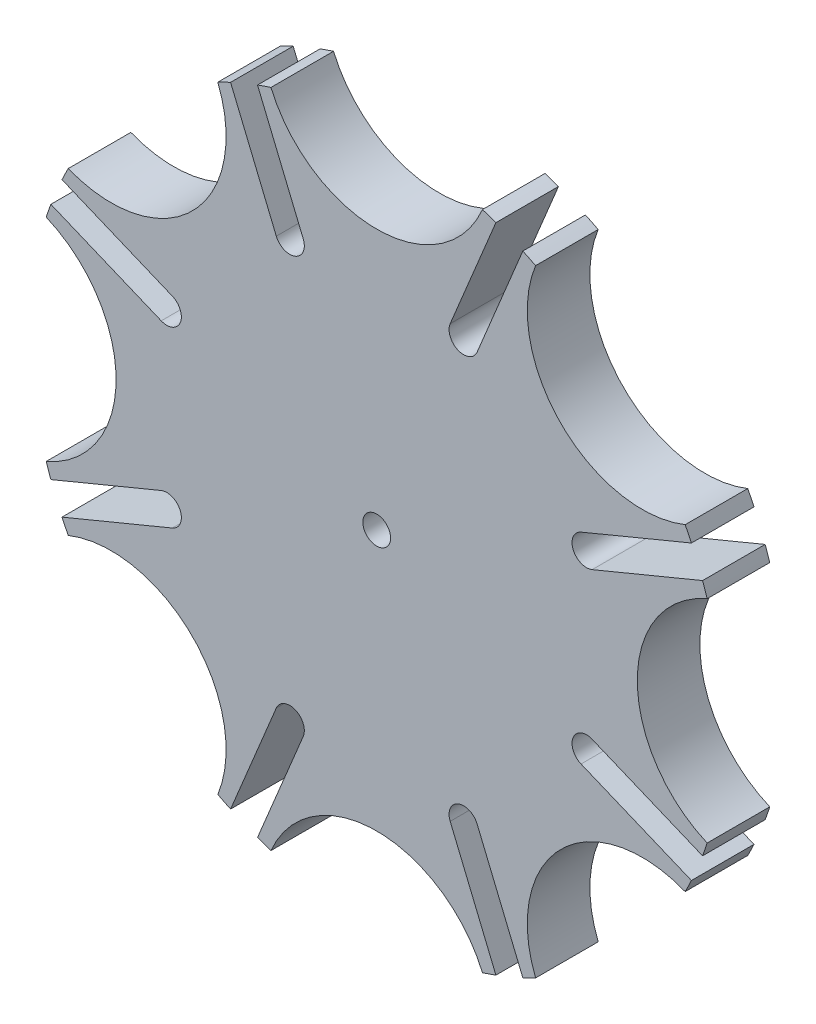
SolidWorks part; units mm, degrees
ref_plane "Front Plane" through (0, 0, 0) normal (0, 0, 1) x (1, 0, 0)
ref_plane "Top Plane" through (0, 0, 0) normal (0, 1, 0) x (1, 0, 0)
ref_plane "Right Plane" through (0, 0, 0) normal (1, 0, 0) x (0, 0, -1)
sketch "Croquis1" plane through (0, 0, 0) normal (0, 0, 1) x (1, 0, 0)
  line L0 (0, 0) -> (-15.1187, 6.2624) construction
  line L1 (0, 0) -> (-18, 0) construction
  line L2 (0, 0) -> (33.8007, 14.0007) construction
  line L3 (0, 0) -> (-10.0606, 4.1672)
  line L4 (-10.0606, 4.1672) -> (-15.364, 6.364) construction
  line L5 (-10.3278, 3.5219) -> (-15.6312, 5.7187)
  line L6 (-9.7933, 4.8125) -> (-15.0967, 7.0092)
  line L7 (-18, 0) -> (-15.364, 6.364) construction
  line L8 (-4.1672, 10.0606) -> (-6.364, 15.364) construction
  line L9 (-4.8125, 9.7933) -> (-7.0092, 15.0967)
  line L10 (-3.5219, 10.3278) -> (-5.7187, 15.6312)
  line L11 (4.1672, 10.0606) -> (6.364, 15.364) construction
  line L12 (3.5219, 10.3278) -> (5.7187, 15.6312)
  line L13 (4.8125, 9.7933) -> (7.0092, 15.0967)
  line L14 (10.0606, 4.1672) -> (15.364, 6.364) construction
  line L45 (-16.2663, 6.7899) -> (-19.2031, 0.5679)
  line L46 (-16.7477, -0.4492) -> (-14.4248, 6.0271)
  line L60 (9.7933, 4.8125) -> (15.0967, 7.0092)
  line L75 (10.3278, 3.5219) -> (15.6312, 5.7187)
  line L82 (10.0606, -4.1672) -> (15.364, -6.364) construction
  line L85 (10.3278, -3.5219) -> (15.6312, -5.7187)
  line L88 (9.7933, -4.8125) -> (15.0967, -7.0092)
  line L91 (4.1672, -10.0606) -> (6.364, -15.364) construction
  line L92 (4.8125, -9.7933) -> (7.0092, -15.0967)
  line L93 (3.5219, -10.3278) -> (5.7187, -15.6312)
  line L94 (-4.1672, -10.0606) -> (-6.364, -15.364) construction
  line L95 (-3.5219, -10.3278) -> (-5.7187, -15.6312)
  line L96 (-4.8125, -9.7933) -> (-7.0092, -15.0967)
  line L97 (-10.0606, -4.1672) -> (-15.364, -6.364) construction
  line L98 (-9.7933, -4.8125) -> (-15.0967, -7.0092)
  line L99 (-10.3278, -3.5219) -> (-15.6312, -5.7187)
  circle A0 centre (0, 0) radius 16.6298
  circle A7 centre (-18, 0) radius 5.5106
  arc A8 (-10.3278, 3.5219) -> (-9.7933, 4.8125) centre (-10.0606, 4.1672) ccw
  arc A9 (-15.0967, 7.0092) -> (-15.6312, 5.7187) centre (-15.364, 6.364) ccw
  circle A10 centre (-12.7279, 12.7279) radius 5.5106
  arc A11 (-4.8125, 9.7933) -> (-3.5219, 10.3278) centre (-4.1672, 10.0606) ccw
  arc A12 (-5.7187, 15.6312) -> (-7.0092, 15.0967) centre (-6.364, 15.364) ccw
  circle A13 centre (0, 18) radius 5.5106
  arc A14 (3.5219, 10.3278) -> (4.8125, 9.7933) centre (4.1672, 10.0606) ccw
  arc A15 (7.0092, 15.0967) -> (5.7187, 15.6312) centre (6.364, 15.364) ccw
  circle A52 centre (-18, 0) radius 1.3304
  circle A53 centre (-15.364, 6.364) radius 0.9978
  circle A54 centre (0, 0) radius 0.6652
  arc A55 (-12.4894, 0) -> (-22.5301, 3.1377) centre (-12.4894, 17.6341) cw
  circle A56 centre (-18, 0) radius 0.6652
  circle A57 centre (-15.364, 6.364) radius 0.6985
  circle A115 centre (12.7279, 12.7279) radius 5.5106
  arc A116 (9.7933, 4.8125) -> (10.3278, 3.5219) centre (10.0606, 4.1672) ccw
  arc A117 (15.6312, 5.7187) -> (15.0967, 7.0092) centre (15.364, 6.364) ccw
  circle A118 centre (18, 0) radius 5.5106
  arc A119 (10.3278, -3.5219) -> (9.7933, -4.8125) centre (10.0606, -4.1672) ccw
  arc A120 (15.0967, -7.0092) -> (15.6312, -5.7187) centre (15.364, -6.364) ccw
  circle A121 centre (12.7279, -12.7279) radius 5.5106
  arc A122 (4.8125, -9.7933) -> (3.5219, -10.3278) centre (4.1672, -10.0606) ccw
  arc A123 (5.7187, -15.6312) -> (7.0092, -15.0967) centre (6.364, -15.364) ccw
  circle A124 centre (0, -18) radius 5.5106
  arc A125 (-3.5219, -10.3278) -> (-4.8125, -9.7933) centre (-4.1672, -10.0606) ccw
  arc A126 (-7.0092, -15.0967) -> (-5.7187, -15.6312) centre (-6.364, -15.364) ccw
  circle A127 centre (-12.7279, -12.7279) radius 5.5106
  arc A128 (-9.7933, -4.8125) -> (-10.3278, -3.5219) centre (-10.0606, -4.1672) ccw
  arc A129 (-15.6312, -5.7187) -> (-15.0967, -7.0092) centre (-15.364, -6.364) ccw
  point P4 (-12.7123, 5.2656)
  point P14 (12.7123, 5.2656)
  point P15 (0, 0)
  point P18 (-15.364, 6.364)
  point P20 (-5.2656, 12.7123)
  point P29 (5.2656, 12.7123)
  point P44 (12.7123, -5.2656)
  point P47 (0, 0)
  point P55 (5.2656, -12.7123)
  point P64 (-5.2656, -12.7123)
  point P73 (-12.7123, -5.2656)
  dimension "D4" = 11.0213
  dimension "D8" = 0.6985
  dimension "D3" = 2.6608
  dimension "D9" = 1.3304
  dimension "D11" = 1.9956
  dimension "D12" = 17.6341
  dimension "D13" = 1.3304
  dimension "D1" = 18
  dimension "D2" = 22.5
  dimension "D5" = 45
  dimension "D6" = 36.5856
  dimension "D7" = 10.8895
  dimension "D10" = 8
extrude "Saliente-Extruir1" add sketch "Croquis1" against normal blind 3 contours A0 L13 A14 L12 A13 L10 A11 L9 A10 L6 A8 L5 A7 | A53 A0 A7 L46 L5 | A0 A53 L5 | L6 A53 A0 region at (-9.0014, 4.6059, 0) region at (-15.2182, 5.0981, 0) region at (-14.7871, 7.0101, 0) region at (-15.4129, 5.4991, 0)
sketch "Croquis4" [suppressed] plane through (0, 0, 0) normal (0, 0, 1) x (1, 0, 0)
  circle A0 centre (-18, 0) radius 5.5106 construction
  arc A1 (-22.5301, 3.1377) -> (-12.4894, 0) centre (-12.4894, 17.6341) ccw construction
  arc A2 (-22.5301, 3.1377) -> (-12.4894, 0) centre (-18, 0) ccw construction
  arc A3 (-22.5301, 3.1377) -> (-12.4894, 0) centre (-12.4894, 17.6341) ccw construction
  circle A4 centre (-18, 0) radius 0.6652 construction
  circle A5 centre (-18, 0) radius 0.6652
  circle A6 centre (-15.364, 6.364) radius 0.6652
  circle A7 centre (-15.364, 6.364) radius 0.6985 construction
  arc A8 (-22.2451, 2.9444) -> (-12.8338, 0.0034) centre (-18, 0) ccw
  circle A9 centre (-15.364, 6.364) radius 0.6985 construction
  arc A10 (-12.8338, 0.0034) -> (-22.2451, 2.9444) centre (-12.4894, 17.6341) cw
  dimension "D1" = 5.1662
extrude "Saliente-Extruir4" [suppressed] add sketch "Croquis4" against normal blind 3
sketch "Croquis6" [suppressed] plane through (0, 0, 0) normal (0, 0, 1) x (1, 0, 0)
  line L0 (-16.7477, -0.4492) -> (-14.4248, 6.0271) construction
  line L1 (-16.2663, 6.7899) -> (-19.2031, 0.5679) construction
  line L2 (-16.7477, -0.4492) -> (-14.4248, 6.0271)
  line L3 (-16.2663, 6.7899) -> (-19.2031, 0.5679)
  circle A0 centre (-15.364, 6.364) radius 0.9978 construction
  circle A1 centre (-18, 0) radius 1.3304 construction
  arc A2 (-14.4248, 6.0271) -> (-16.2663, 6.7899) centre (-15.364, 6.364) ccw
  arc A3 (-19.2031, 0.5679) -> (-16.7477, -0.4492) centre (-18, 0) ccw
  circle A6 centre (-18, 0) radius 0.6652 construction
  circle A7 centre (-18, 0) radius 0.6652
extrude "Saliente-Extruir5" [suppressed] add sketch "Croquis6" along normal blind 3
sketch "Croquis7" [suppressed] plane through (0, 0, 0) normal (0, 0, 1) x (1, 0, 0)
  circle A0 centre (0, 0) radius 0.6766 construction
  circle A1 centre (-18, 0) radius 0.6766 construction
  circle A2 centre (0, 0) radius 0.6766
  circle A3 centre (-18, 0) radius 0.6766
extrude "Saliente-Extruir6" [suppressed] add sketch "Croquis7" against normal blind 18 and the other way blind 3
sketch "Croquis8" [suppressed] plane through (0, 0, -18) normal (0, 0, -1) x (-1, 0, 0)
  line L0 (0, -4.9251) -> (18, -4.9251)
  line L1 (0, 4.9251) -> (18, 4.9251)
  circle A0 centre (18, 0) radius 4.9251 construction
  arc A1 (18, -4.9251) -> (18, 4.9251) centre (18, 0) ccw
  arc A2 (0, 4.9251) -> (0, -4.9251) centre (0, 0) ccw
extrude "Saliente-Extruir7" [suppressed] add sketch "Croquis8" along normal blind 6
equation "\"S\"= ( \"d\" - \"a\" ) * 0.98"
equation "\"R\"= \"d\" * cos ( \"Bo\" / 2 ) * 2"
equation "\"n\"= 8"
equation "\"Bo\"= 360 / \"n\""
equation "\"din\"= \"d\" / 10"
equation "\"d\"=18"
equation "\"D4@Croquis1\"= \"D2\""
equation "\"D1@Croquis1\"=\"d\""
equation "\"D2@Croquis1\"=\"Bo\"/2"
equation "\"D5@Croquis1\"=\"Bo\""
equation "\"D6@Croquis1\"=\"R\"*1.1"
equation "\"D7@Croquis1\"=\"S\""
equation "\"R1\"= \"R\" / 50"
equation "\"D8@Croquis1\"=\"R1\"*1.05"
equation "\"a\"= \"d\" * sin ( \"Bo\" / 2 )"
equation "\"ancho\"= 3"
equation "\"D1@Saliente-Extruir1\"=\"ancho\""
equation "\"D10@Croquis1\"=\"n\""
equation "\"D2\"= 1.6 * \"a\""
equation "\"D3@Croquis1\"=4*\"R1\""
equation "\"D9@Croquis1\"=2*\"R1\""
equation "\"D11@Croquis1\"=3*\"R1\""
equation "\"D12@Croquis1\"=\"D2\"/2*3.2"
equation "\"D13@Croquis1\"=2*\"R1\""
equation "\"D1@Saliente-Extruir7\"=\"ancho\"*2"
equation "\"D1@Saliente-Extruir6\"=\"ancho\"*6"
equation "\"D2@Saliente-Extruir6\"=\"ancho\""
equation "\"D1@Saliente-Extruir5\"=\"ancho\""
equation "\"D1@Saliente-Extruir4\"=\"ancho\""
equation "\"D1@Croquis4\"=\"a\"*0.75"
